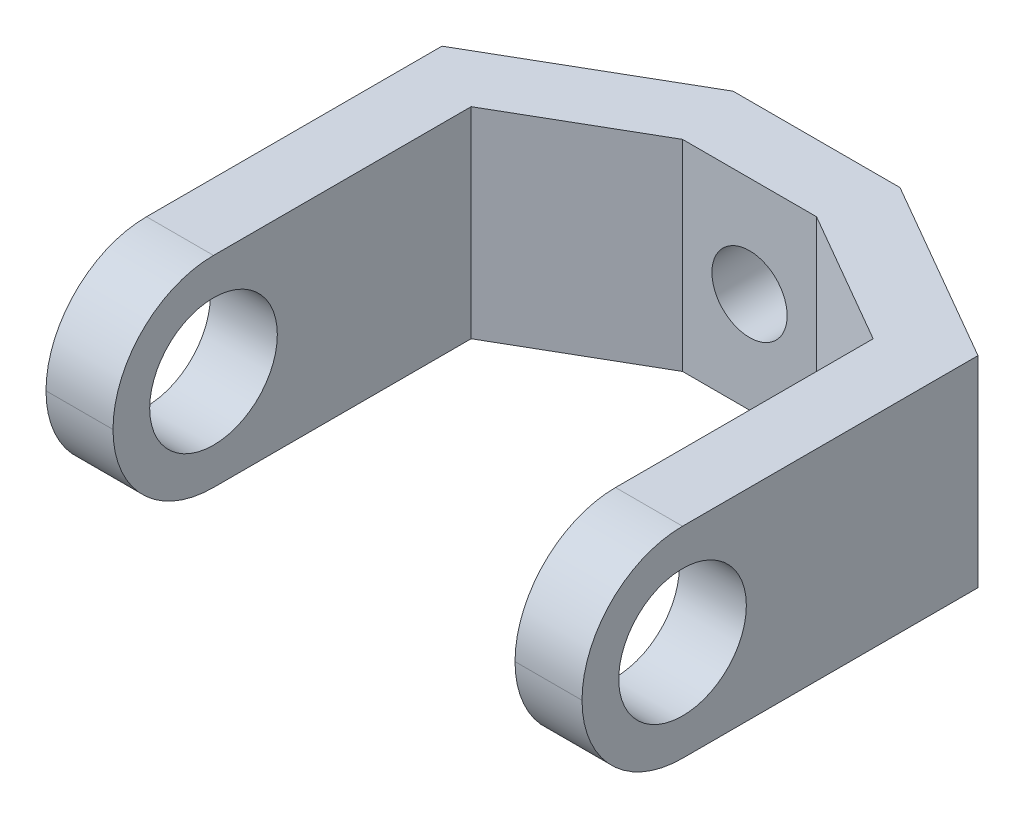
SolidWorks part; units mm, degrees
material "ABS"
ref_plane "Front Plane" through (0, 0, 0) normal (0, 0, 1) x (1, 0, 0)
ref_plane "Top Plane" through (0, 0, 0) normal (0, 1, 0) x (1, 0, 0)
ref_plane "Right Plane" through (0, 0, 0) normal (1, 0, 0) x (0, 0, -1)
sketch "Sketch1" plane through (0, 0, 0) normal (0, 1, 0) x (1, 0, 0)
  line L0 (-15, -7.5) -> (-20, -7.5)
  line L1 (-20, -7.5) -> (-20, 22.0494)
  line L2 (-20, 22.0494) -> (-6.2291, 30)
  line L3 (-6.2291, 30) -> (6.2291, 30)
  line L4 (6.2291, 30) -> (20, 22.0494)
  line L5 (20, 22.0494) -> (20, -7.5)
  line L6 (20, -7.5) -> (15, -7.5)
  line L7 (15, -7.5) -> (15, 19.2265)
  line L8 (15, 19.2265) -> (5, 25)
  line L9 (5, 25) -> (-5, 25)
  line L10 (-5, 25) -> (-15, 19.2265)
  line L11 (-15, 19.2265) -> (-15, -7.5)
  line L12 (-10, 22.1132) -> (-13.1146, 26.0247) construction
  line L14 (13.1146, 26.0247) -> (10, 22.1132) construction
  line L16 (0, 25) -> (0, 30) construction
  point P5 (0, 25)
  dimension "D1" = 5
  dimension "D2" = 30
  dimension "D3" = 25
  dimension "D4" = 150
  dimension "D5" = 10
  dimension "D6" = 7.5
extrude "Boss-Extrude1" add sketch "Sketch1" along normal mid plane 15
sketch "Sketch3" plane through (0, 0, 0) normal (1, 0, 0) x (0, 0, -1)
  circle A0 centre (0, 0) radius 4.7625
  dimension "D1" = 9.525
extrude "Cut-Extrude1" cut sketch "Sketch3" against normal through all both and the other way through all
fillet "Fillet1" radius 7.5 4 edges at (17.5, 7.5, 7.5) (17.5, -7.5, 7.5) (-17.5, -7.5, 7.5) (-17.5, 7.5, 7.5)
sketch "Sketch4" plane through (0, 0, 0) normal (0, 0, 1) x (1, 0, 0)
  circle A0 centre (0, 0) radius 2.8067
  dimension "D1" = 5.6134
extrude "Cut-Extrude2" cut sketch "Sketch4" against normal through all
